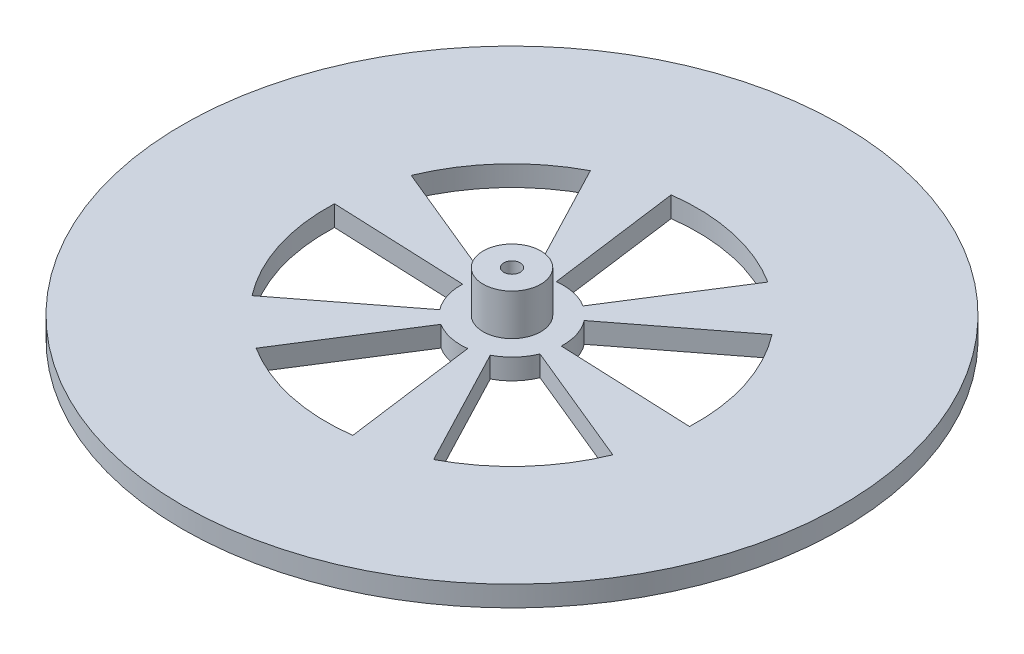
SolidWorks part; units mm, degrees
ref_plane "前视基准面" through (0, 0, 0) normal (0, 0, 1) x (1, 0, 0)
ref_plane "上视基准面" through (0, 0, 0) normal (0, 1, 0) x (1, 0, 0)
ref_plane "右视基准面" through (0, 0, 0) normal (1, 0, 0) x (0, 0, -1)
other "Configuration Table"
sketch "草图1" plane through (0, 0, 0) normal (0, 1, 0) x (1, 0, 0)
  circle A0 centre (0, 0) radius 80
  dimension "D1" = 160
extrude "凸台-拉伸1" add sketch "草图1" along normal blind 5
sketch "草图2" plane through (0, 5, 0) normal (0, 1, 0) x (1, 0, 0)
  circle A0 centre (0, 0) radius 2
  circle A1 centre (0, 0) radius 7
  dimension "D1" = 4
sketch "草图3" plane through (0, 5, 0) normal (0, 1, 0) x (1, 0, 0)
  line L0 (-43.9519, 9.6554) -> (0, 0)
  line L1 (0, 0) -> (-13.6141, 42.8912)
  line L3 (-11.5577, 4.7614) -> (-41.6076, 17.1409)
  line L4 (-5.7931, 11.0765) -> (-20.8553, 39.8755)
  arc A0 (-63.4861, 13.9468) -> (-34.9885, -54.7796) centre (0, 0) cw
  circle A3 centre (0, 0) radius 45
  circle A4 centre (0, 0) radius 12.5
  point P8 (-43.9519, 9.6554)
  point P10 (-13.6141, 42.8912)
  dimension "D4" = 10
  dimension "D1" = 60
  dimension "D3" = 45
sketch "草图5" plane through (0, 5, 0) normal (0, 1, 0) x (1, 0, 0)
  line L0 (-41.6076, 17.1409) -> (-11.5577, 4.7614)
  line L1 (-20.8553, 39.8755) -> (-5.7931, 11.0765)
  arc A0 (-20.8553, 39.8755) -> (-41.6076, 17.1409) centre (0, 0) ccw
  arc A1 (-5.7931, 11.0765) -> (-11.5577, 4.7614) centre (0, 0) ccw
extrude "切除-拉伸3" cut sketch "草图5" against normal through all
ref_axis "基准轴1" through (0, 5, 0) along (0, 1, 0)
pattern_circular "阵列(圆周)2" count 6 over 360 about axis through (0, 5, 0) along (0, 1, 0) of "切除-拉伸3"
extrude "凸台-拉伸2" add sketch "草图2" along normal blind 10
